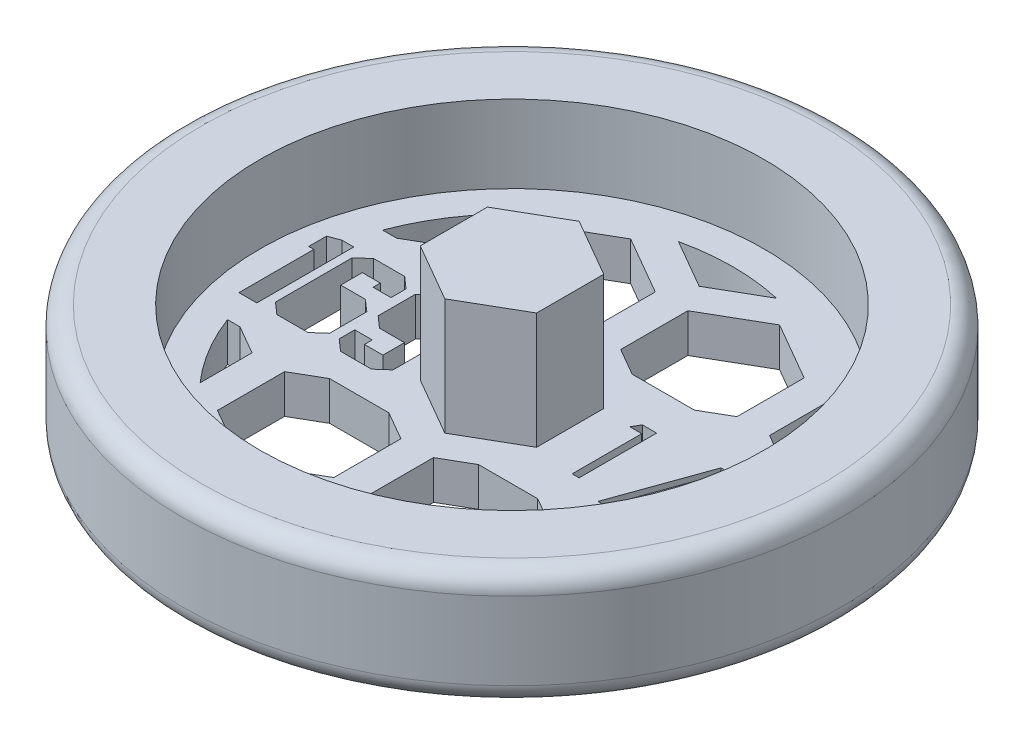
SolidWorks part; units mm, degrees
ref_plane "Front Plane" through (0, 0, 0) normal (0, 0, 1) x (1, 0, 0)
ref_plane "Top Plane" through (0, 0, 0) normal (0, 1, 0) x (1, 0, 0)
ref_plane "Right Plane" through (0, 0, 0) normal (1, 0, 0) x (0, 0, -1)
sketch "Sketch1" plane through (0, 0, 0) normal (0, 0, 1) x (1, 0, 0)
  line L0 (0, 0) -> (25.4, 0)
  line L1 (26.9875, 1.5875) -> (26.9875, 7.9375)
  line L2 (25.4, 9.525) -> (20.6375, 9.525)
  line L3 (20.6375, 9.525) -> (20.6375, 3.175)
  line L4 (20.6375, 3.175) -> (0, 3.175)
  line L5 (0, 3.175) -> (0, 0)
  arc A0 (25.4, 0) -> (26.9875, 1.5875) centre (25.4, 1.5875) ccw
  arc A1 (26.9875, 7.9375) -> (25.4, 9.525) centre (25.4, 7.9375) ccw
  dimension "D5" = 1.5875
  dimension "D1" = 3.175
  dimension "D2" = 6.35
  dimension "D3" = 20.6375
  dimension "D4" = 6.35
revolve "Revolve1" add sketch "Sketch1" angle 360 about L5
sketch "Sketch2" plane through (0, 3.175, 0) normal (0, 1, 0) x (1, 0, 0)
  line L1 (0, 5.4993) -> (-4.7625, 2.7496)
  line L2 (-4.7625, 2.7496) -> (-4.7625, -2.7496)
  line L3 (-4.7625, -2.7496) -> (0, -5.4993)
  line L4 (0, -5.4993) -> (4.7625, -2.7496)
  line L5 (4.7625, -2.7496) -> (4.7625, 2.7496)
  line L6 (4.7625, 2.7496) -> (0, 5.4993)
  circle A0 centre (0, 0) radius 4.7625 construction
  dimension "D1" = 9.525
extrude "Boss-Extrude1" add sketch "Sketch2" along normal blind 9.525
sketch "Sketch3" plane through (0, 3.175, 0) normal (0, 1, 0) x (1, 0, 0)
  line L0 (-4.7625, 0) -> (-20.6375, 0) construction
  line L1 (-4.7625, 2.7496) -> (-4.7625, -2.7496) construction
  line L2 (-4.7625, -3.9688) -> (-20.6375, -3.9688) construction
  line L3 (4.7625, 0) -> (20.6375, 0) construction
  line L4 (4.7625, -2.7496) -> (4.7625, 2.7496) construction
  line L5 (4.7625, -3.175) -> (20.6375, -3.175) construction
  circle A0 centre (0, 0) radius 20.6375 construction
  text T0 "169" font "Jersey M54" height 7.9375
  text T1 "1/4" font "Century Gothic" height 6.35
  dimension "D1" = 3.9688
  dimension "D2" = 3.175
extrude "Cut-Extrude1" cut sketch "Sketch3" against normal through all both and the other way through all body kept at (25.4, 0, 0) body kept at (17.8696, 0, 1.0583)
sketch "Sketch4" plane through (0, 3.175, 0) normal (0, 1, 0) x (1, 0, 0)
  line L0 (0, -6.35) -> (0, 6.35)
  line L1 (-16.9469, 6.35) -> (16.9469, 6.35)
  line L2 (-16.9469, -6.35) -> (16.9469, -6.35)
  line L3 (7.4295, -2.7496) -> (12.192, -5.4993)
  line L4 (0, -5.4993) -> (4.7625, -2.7496)
  line L5 (4.7625, -2.7496) -> (4.7625, 2.7496)
  line L6 (4.7625, 2.7496) -> (0, 5.4993)
  line L7 (0, 5.4993) -> (-4.7625, 2.7496)
  line L8 (-4.7625, 2.7496) -> (-4.7625, -2.7496)
  line L9 (-4.7625, -2.7496) -> (0, -5.4993)
  line L10 (6.0325, -15.9479) -> (10.795, -13.1982)
  line L11 (10.795, -13.1982) -> (10.795, -7.699)
  line L12 (10.795, -7.699) -> (6.0325, -4.9493)
  line L13 (6.0325, -4.9493) -> (1.27, -7.699)
  line L14 (1.27, -7.699) -> (1.27, -13.1982)
  line L15 (1.27, -13.1982) -> (6.0325, -15.9479)
  line L16 (7.4295, 2.7496) -> (7.4295, -2.7496)
  line L17 (12.192, 5.4993) -> (7.4295, 2.7496)
  line L18 (16.9545, 2.7496) -> (12.192, 5.4993)
  line L19 (16.9545, -2.7496) -> (16.9545, 2.7496)
  line L20 (12.192, -5.4993) -> (16.9545, -2.7496)
  line L21 (18.2245, -15.9479) -> (22.987, -13.1982)
  line L22 (22.987, -13.1982) -> (22.987, -7.699)
  line L23 (22.987, -7.699) -> (18.2245, -4.9493)
  line L24 (18.2245, -4.9493) -> (13.462, -7.699)
  line L25 (13.462, -7.699) -> (13.462, -13.1982)
  line L26 (13.462, -13.1982) -> (18.2245, -15.9479)
  line L27 (-16.9545, -2.7496) -> (-12.192, -5.4993)
  line L28 (-16.9545, 2.7496) -> (-16.9545, -2.7496)
  line L29 (-12.192, 5.4993) -> (-16.9545, 2.7496)
  line L30 (-7.4295, 2.7496) -> (-12.192, 5.4993)
  line L31 (-7.4295, -2.7496) -> (-7.4295, 2.7496)
  line L32 (-12.192, -5.4993) -> (-7.4295, -2.7496)
  line L33 (-6.1595, -15.9479) -> (-1.397, -13.1982)
  line L34 (-1.397, -13.1982) -> (-1.397, -7.699)
  line L35 (-1.397, -7.699) -> (-6.1595, -4.9493)
  line L36 (-6.1595, -4.9493) -> (-10.922, -7.699)
  line L37 (-10.922, -7.699) -> (-10.922, -13.1982)
  line L38 (-10.922, -13.1982) -> (-6.1595, -15.9479)
  line L39 (-29.1465, -2.7496) -> (-24.384, -5.4993)
  line L40 (-29.1465, 2.7496) -> (-29.1465, -2.7496)
  line L41 (-24.384, 5.4993) -> (-29.1465, 2.7496)
  line L42 (-19.6215, 2.7496) -> (-24.384, 5.4993)
  line L43 (-19.6215, -2.7496) -> (-19.6215, 2.7496)
  line L44 (-24.384, -5.4993) -> (-19.6215, -2.7496)
  line L45 (-18.3515, -15.9479) -> (-13.589, -13.1982)
  line L46 (-13.589, -13.1982) -> (-13.589, -7.699)
  line L47 (-13.589, -7.699) -> (-18.3515, -4.9493)
  line L48 (-18.3515, -4.9493) -> (-23.114, -7.699)
  line L49 (-23.114, -7.699) -> (-23.114, -13.1982)
  line L50 (-23.114, -13.1982) -> (-18.3515, -15.9479)
  line L51 (-4.7625, 18.0784) -> (0, 15.3287)
  line L52 (-4.7625, 23.5776) -> (-4.7625, 18.0784)
  line L53 (0, 26.3273) -> (-4.7625, 23.5776)
  line L54 (4.7625, 23.5776) -> (0, 26.3273)
  line L55 (4.7625, 18.0784) -> (4.7625, 23.5776)
  line L56 (0, 15.3287) -> (4.7625, 18.0784)
  line L57 (6.0325, 4.8801) -> (10.795, 7.6298)
  line L58 (10.795, 7.6298) -> (10.795, 13.129)
  line L59 (10.795, 13.129) -> (6.0325, 15.8787)
  line L60 (6.0325, 15.8787) -> (1.27, 13.129)
  line L61 (1.27, 13.129) -> (1.27, 7.6298)
  line L62 (1.27, 7.6298) -> (6.0325, 4.8801)
  line L63 (-16.9545, 18.0784) -> (-12.192, 15.3287)
  line L64 (-12.192, 15.3287) -> (-7.4295, 18.0784)
  line L65 (-7.4295, 18.0784) -> (-7.4295, 23.5776)
  line L66 (-7.4295, 23.5776) -> (-12.192, 26.3273)
  line L67 (-12.192, 26.3273) -> (-16.9545, 23.5776)
  line L68 (-16.9545, 23.5776) -> (-16.9545, 18.0784)
  line L69 (-29.1465, 18.0784) -> (-24.384, 15.3287)
  line L70 (-24.384, 15.3287) -> (-19.6215, 18.0784)
  line L71 (-19.6215, 18.0784) -> (-19.6215, 23.5776)
  line L72 (-19.6215, 23.5776) -> (-24.384, 26.3273)
  line L73 (-24.384, 26.3273) -> (-29.1465, 23.5776)
  line L74 (-29.1465, 23.5776) -> (-29.1465, 18.0784)
  line L75 (-18.3515, 4.8801) -> (-13.589, 7.6298)
  line L76 (-13.589, 7.6298) -> (-13.589, 13.129)
  line L77 (-13.589, 13.129) -> (-18.3515, 15.8787)
  line L78 (-18.3515, 15.8787) -> (-23.114, 13.129)
  line L79 (-23.114, 13.129) -> (-23.114, 7.6298)
  line L80 (-23.114, 7.6298) -> (-18.3515, 4.8801)
  line L81 (18.2245, 4.8801) -> (22.987, 7.6298)
  line L82 (22.987, 7.6298) -> (22.987, 13.129)
  line L83 (22.987, 13.129) -> (18.2245, 15.8787)
  line L84 (18.2245, 15.8787) -> (13.462, 13.129)
  line L85 (13.462, 13.129) -> (13.462, 7.6298)
  line L86 (13.462, 7.6298) -> (18.2245, 4.8801)
  line L87 (7.4295, 18.0784) -> (12.192, 15.3287)
  line L88 (12.192, 15.3287) -> (16.9545, 18.0784)
  line L89 (16.9545, 18.0784) -> (16.9545, 23.5776)
  line L90 (16.9545, 23.5776) -> (12.192, 26.3273)
  line L91 (12.192, 26.3273) -> (7.4295, 23.5776)
  line L92 (7.4295, 23.5776) -> (7.4295, 18.0784)
  line L93 (-6.1595, 4.8801) -> (-1.397, 7.6298)
  line L94 (-1.397, 7.6298) -> (-1.397, 13.129)
  line L95 (-1.397, 13.129) -> (-6.1595, 15.8787)
  line L96 (-6.1595, 15.8787) -> (-10.922, 13.129)
  line L97 (-10.922, 13.129) -> (-10.922, 7.6298)
  line L98 (-10.922, 7.6298) -> (-6.1595, 4.8801)
  line L99 (-4.7625, -23.5776) -> (0, -26.3273)
  line L100 (-4.7625, -18.0784) -> (-4.7625, -23.5776)
  line L101 (0, -15.3287) -> (-4.7625, -18.0784)
  line L102 (4.7625, -18.0784) -> (0, -15.3287)
  line L103 (4.7625, -23.5776) -> (4.7625, -18.0784)
  line L104 (0, -26.3273) -> (4.7625, -23.5776)
  line L105 (6.0325, -36.7759) -> (10.795, -34.0262)
  line L106 (10.795, -34.0262) -> (10.795, -28.527)
  line L107 (10.795, -28.527) -> (6.0325, -25.7773)
  line L108 (6.0325, -25.7773) -> (1.27, -28.527)
  line L109 (1.27, -28.527) -> (1.27, -34.0262)
  line L110 (1.27, -34.0262) -> (6.0325, -36.7759)
  line L111 (-16.9545, -23.5776) -> (-12.192, -26.3273)
  line L112 (-12.192, -26.3273) -> (-7.4295, -23.5776)
  line L113 (-7.4295, -23.5776) -> (-7.4295, -18.0784)
  line L114 (-7.4295, -18.0784) -> (-12.192, -15.3287)
  line L115 (-12.192, -15.3287) -> (-16.9545, -18.0784)
  line L116 (-16.9545, -18.0784) -> (-16.9545, -23.5776)
  line L117 (-29.1465, -23.5776) -> (-24.384, -26.3273)
  line L118 (-24.384, -26.3273) -> (-19.6215, -23.5776)
  line L119 (-19.6215, -23.5776) -> (-19.6215, -18.0784)
  line L120 (-19.6215, -18.0784) -> (-24.384, -15.3287)
  line L121 (-24.384, -15.3287) -> (-29.1465, -18.0784)
  line L122 (-29.1465, -18.0784) -> (-29.1465, -23.5776)
  line L123 (-18.3515, -36.7759) -> (-13.589, -34.0262)
  line L124 (-13.589, -34.0262) -> (-13.589, -28.527)
  line L125 (-13.589, -28.527) -> (-18.3515, -25.7773)
  line L126 (-18.3515, -25.7773) -> (-23.114, -28.527)
  line L127 (-23.114, -28.527) -> (-23.114, -34.0262)
  line L128 (-23.114, -34.0262) -> (-18.3515, -36.7759)
  line L129 (18.2245, -36.7759) -> (22.987, -34.0262)
  line L130 (22.987, -34.0262) -> (22.987, -28.527)
  line L131 (22.987, -28.527) -> (18.2245, -25.7773)
  line L132 (18.2245, -25.7773) -> (13.462, -28.527)
  line L133 (13.462, -28.527) -> (13.462, -34.0262)
  line L134 (13.462, -34.0262) -> (18.2245, -36.7759)
  line L135 (7.4295, -23.5776) -> (12.192, -26.3273)
  line L136 (12.192, -26.3273) -> (16.9545, -23.5776)
  line L137 (16.9545, -23.5776) -> (16.9545, -18.0784)
  line L138 (16.9545, -18.0784) -> (12.192, -15.3287)
  line L139 (12.192, -15.3287) -> (7.4295, -18.0784)
  line L140 (7.4295, -18.0784) -> (7.4295, -23.5776)
  line L141 (-6.1595, -36.7759) -> (-1.397, -34.0262)
  line L142 (-1.397, -34.0262) -> (-1.397, -28.527)
  line L143 (-1.397, -28.527) -> (-6.1595, -25.7773)
  line L144 (-6.1595, -25.7773) -> (-10.922, -28.527)
  line L145 (-10.922, -28.527) -> (-10.922, -34.0262)
  line L146 (-10.922, -34.0262) -> (-6.1595, -36.7759)
  circle A0 centre (0, 0) radius 18.0975
  circle A1 centre (0, 0) radius 4.7625 construction
  circle A2 centre (6.0325, -10.4486) radius 4.7625 construction
  point P6 (0, 0)
  point P9 (0, 6.35)
  point P12 (0, -6.35)
  dimension "D1" = 36.195
  dimension "D2" = 12.7
  dimension "D3" = 9.525
  dimension "D4" = 2.54
  dimension "D5" = 9.525
  dimension "D6" = 1.27
  dimension "D7" = 2
  dimension "D8" = 3
  dimension "D9" = 2
  dimension "D10" = 2
extrude "Cut-Extrude2" cut sketch "Sketch4" against normal through all both and the other way through all contours L76 A0 L1 L75 | L97 L98 L1 L93 L94 L95 L96 | L56 A0 L51 | L61 L62 L1 L57 L58 L59 L60 | L1 A0 L85 L86 | L14 L15 L10 L11 L12 L2 L13 | L25 A0 L2 L24 | L101 A0 L102 | L37 L38 L33 L34 L35 L2 L36 | L2 A0 L46 L47 region at (-6.1595, 3.175, 10.655) region at (6.0325, 3.175, 10.655) region at (-14.861, 3.175, 8.6035) region at (14.7836, 3.175, 8.6463) region at (-6.1595, 3.175, -10.6054) region at (6.0325, 3.175, -10.6054) region at (-14.8588, 3.175, -8.5765) region at (14.7807, 3.175, -8.6205) region at (0, 3.175, 17.0707) region at (0, 3.175, -17.0707)
